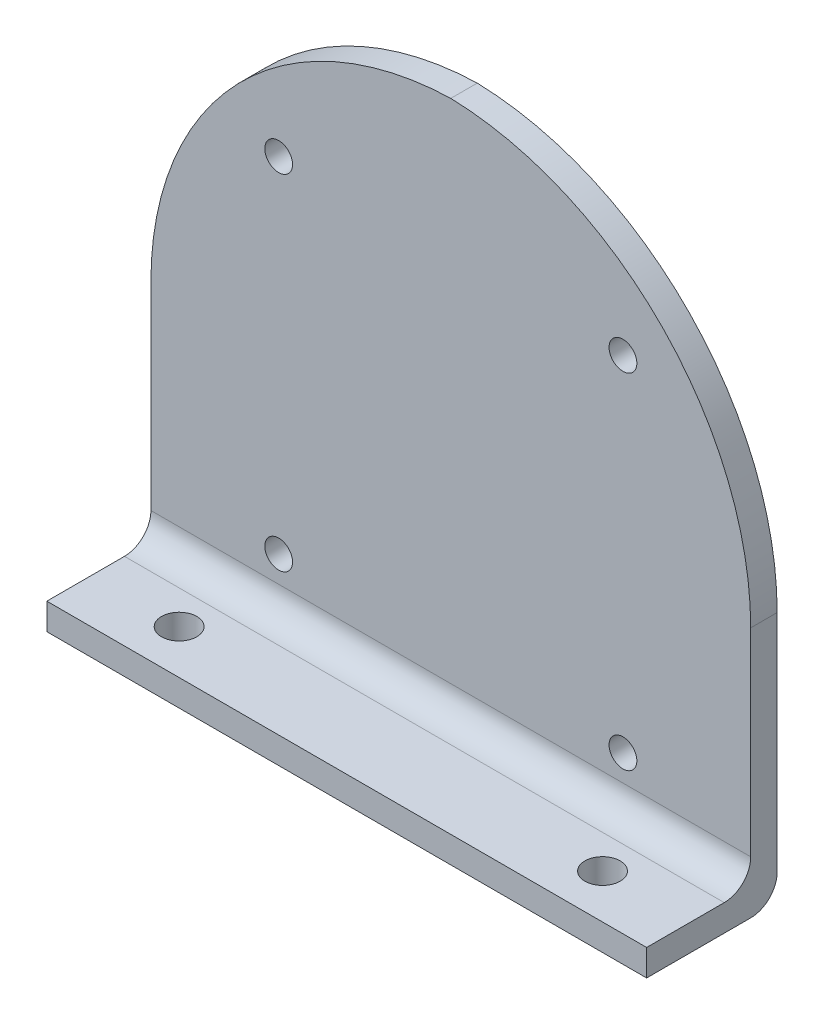
SolidWorks part; units mm, degrees
material "1060-H18"
ref_plane "前视基准面" through (0, 0, 0) normal (0, 0, 1) x (1, 0, 0)
ref_plane "上视基准面" through (0, 0, 0) normal (0, 1, 0) x (1, 0, 0)
ref_plane "右视基准面" through (0, 0, 0) normal (1, 0, 0) x (0, 0, -1)
sketch "草图1" plane through (0, 0, 0) normal (0, 0, 1) x (1, 0, 0)
  line L1 (-34, -40) -> (34, -40)
  line L2 (-34, -40) -> (-34, 40)
  line L3 (-34, 40) -> (34, 40)
  line L4 (34, -40) -> (34, 40)
  line L5 (-34, -40) -> (34, 40) construction
  line L6 (-34, 40) -> (34, -40) construction
  point P0 (0, 0)
  dimension "D1" = 68
  dimension "D2" = 80
extrude "凸台-拉伸1" add sketch "草图1" along normal blind 3
sketch "草图2" plane through (0, 0, 3) normal (0, 0, 1) x (1, 0, 0)
  line L0 (-45.0002, -40.0002) -> (45.0002, 50.0002) construction
  line L1 (-45.0002, 50.0002) -> (45.0002, -40.0002) construction
  circle A0 centre (0, 5) radius 27.6 construction
  circle A1 centre (-19.5161, 24.5161) radius 1.575
  circle A2 centre (19.5161, 24.5161) radius 1.575
  circle A3 centre (-19.5161, -14.5161) radius 1.575
  circle A4 centre (19.5161, -14.5161) radius 1.575
  point P14 (0, 0)
  point P15 (0, 5)
  point P17 (0, 0)
  point P18 (0, 5)
  point P19 (-19.5161, 24.5161)
  point P20 (19.5161, 24.5161)
  point P21 (19.5161, -14.5161)
  point P22 (-19.5161, -14.5161)
  point P23 (-19.5161, -14.5161)
  dimension "D1" = 55.2
  dimension "D2" = 3.15
  dimension "D3" = 5
  dimension "D4" = 90.0003
  dimension "D5" = 90.0003
  dimension "D6" = 90.0003
extrude "切除-拉伸1" cut sketch "草图2" against normal through all
sketch "草图4" plane through (0, 0, 3) normal (0, 0, 1) x (1, 0, 0)
  line L0 (-34, -23.48) -> (34, -23.48)
  line L4 (34, -40) -> (34, 40)
  line L5 (34, 40) -> (-34, 40)
  line L6 (-34, 40) -> (-34, -40)
  line L7 (-34, -40) -> (34, -40)
  line L8 (34, -40) -> (34, -23.48)
  line L10 (-34, -23.48) -> (-34, -40)
  line L11 (-34, -40) -> (34, -40)
  dimension "D2" = 16.52
  dimension "D1" = 0
extrude "切除-拉伸2" cut sketch "草图4" against normal through all
sketch "草图5" plane through (0, 0, 3) normal (0, 0, 1) x (1, 0, 0)
  line L0 (-34, 40) -> (-34, -23.48) construction
  line L1 (34, -23.48) -> (34, 40) construction
  line L2 (34, -23.48) -> (-34, -23.48) construction
  line L3 (-34, -20.48) -> (-34, -23.48)
  line L4 (34, -23.48) -> (34, -20.48)
  line L5 (34, -23.48) -> (-34, -23.48)
  line L6 (-34, -20.48) -> (34, -20.48)
  dimension "D1" = 3
extrude "凸台-拉伸2" add sketch "草图5" along normal blind 11.8
fillet "圆角1" radius 3 2 edges at (0, -20.48, 3) (0, -23.48, 0)
sketch "草图6" plane through (0, -20.48, 0) normal (0, 1, 0) x (1, 0, 0)
  line L0 (24, -9.8) -> (-24, -9.8) construction
  line L1 (34, -14.8) -> (-34, -14.8) construction
  circle A0 centre (24, -9.8) radius 2
  circle A1 centre (-24, -9.8) radius 2
  point P4 (0, -9.8)
  point P7 (0, -14.8)
  point P11 (0, 0)
  point P12 (0, 0)
  dimension "D1" = 4
  dimension "D2" = 48
  dimension "D3" = 5
extrude "切除-拉伸3" cut sketch "草图6" against normal blind 14.5
fillet "圆角2" radius 35 2 edges at (34, 40, 1.5) (-34, 40, 1.5)
